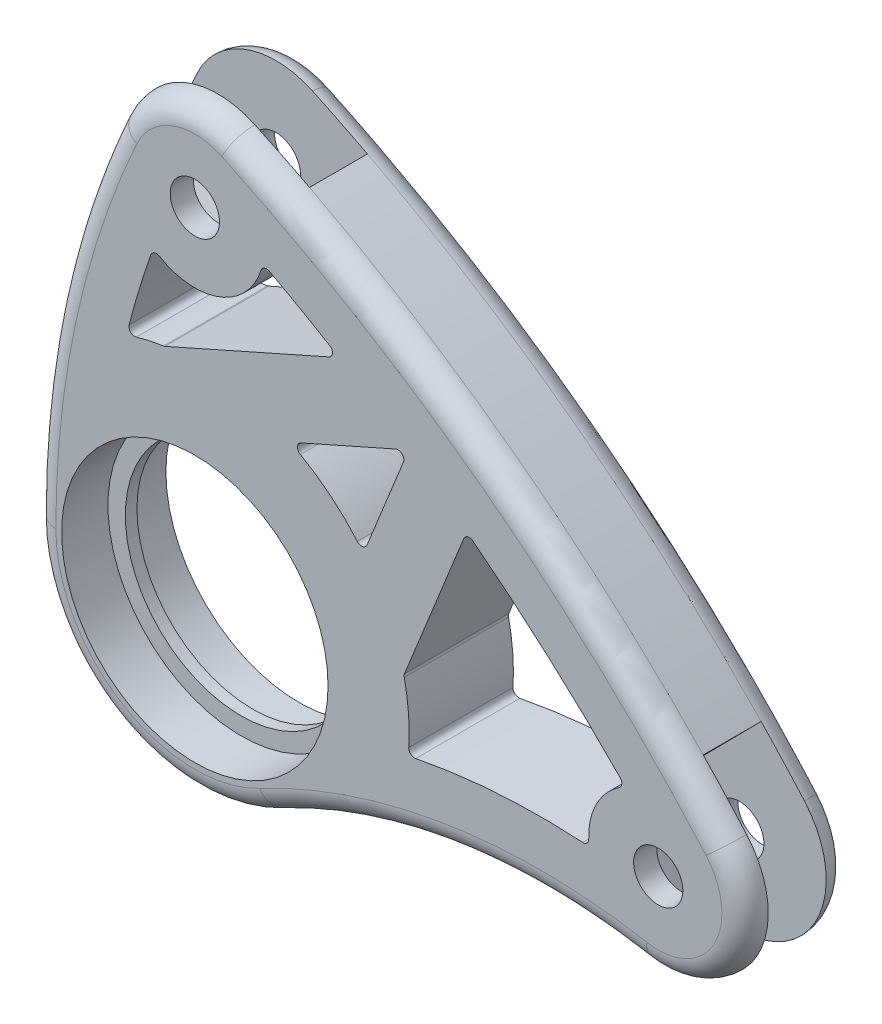
SolidWorks part; units mm, degrees
ref_plane "Front Plane" through (0, 0, 0) normal (0, 0, 1) x (1, 0, 0)
ref_plane "Top Plane" through (0, 0, 0) normal (0, 1, 0) x (1, 0, 0)
ref_plane "Right Plane" through (0, 0, 0) normal (1, 0, 0) x (0, 0, -1)
sketch "Sketch1" plane through (0, 0, 0) normal (0, 0, 1) x (1, 0, 0)
  line L0 (0, 0) -> (0, 55.2821) construction
  line L2 (40, 0) -> (0, 0) construction
  line L4 (0, 30) -> (0, 0) construction
  circle A0 centre (0, 0) radius 11.5
  circle A1 centre (0, 0) radius 14
  circle A2 centre (0, 30) radius 7.5
  circle A3 centre (40, 0) radius 7.5
  arc A4 (6.5345, -12.3815) -> (38.6789, -7.3827) centre (29.8719, -56.601) cw
  arc A5 (-6.8276, 33.1039) -> (-14, 0.0009) centre (66, -0.0042) ccw
  arc A6 (3.1808, 36.7921) -> (45.6298, 4.9554) centre (-51.9531, -80.9375) cw
  dimension "D1" = 23
  dimension "D2" = 28
  dimension "D5" = 90
  dimension "D6" = 80
  dimension "D7" = 50
  dimension "D8" = 130
  dimension "D9" = 15
  dimension "D3" = 40
  dimension "D4" = 30
extrude "Boss-Extrude1" add sketch "Sketch1" along normal blind 9 contours A6 A2 A5 A1 A4 A3 | A2 | A3 | A0 | A1 A0 region at (0, 0, 0) region at (11.6501, -7.0245, 0) region at (15.8028, 12.5336, 0) region at (0, 30, 0) region at (40, 0, 0)
sketch "Sketch2" plane through (0, 0, 9) normal (0, 0, 1) x (1, 0, 0)
  circle A4 centre (0, 0) radius 10
  dimension "D1" = 20
extrude "Cut-Extrude2" cut sketch "Sketch2" against normal through all contours A4 region at (0, 0, 9)
sketch "Sketch3" plane through (0, 0, 9) normal (0, 0, 1) x (1, 0, 0)
  circle A0 centre (0, 0) radius 11.5
  dimension "D1" = 23
extrude "Cut-Extrude3" cut sketch "Sketch3" against normal blind 4
sketch "Sketch4" plane through (0, 0, 0) normal (0, 0, -1) x (-1, 0, 0)
  circle A0 centre (0, 0) radius 11.5
  dimension "D1" = 23
extrude "Cut-Extrude4" cut sketch "Sketch4" against normal blind 4
sketch "Sketch6" plane through (0, 0, 9) normal (0, 0, 1) x (1, 0, 0)
  circle A0 centre (0, 30) radius 2.125
  circle A1 centre (40, 0) radius 2.125
  dimension "D1" = 4.25
extrude "Cut-Extrude5" cut sketch "Sketch6" against normal through all contours A1 | A0 region at (40, 0, 9)
sketch "Sketch7" plane through (0, 0, 9) normal (0, 0, 1) x (1, 0, 0)
  line L1 (18.4682, 21.1255) -> (14.5474, 11.4291)
  line L2 (-6.0691, 16.79) -> (12.4582, 25.0209)
  line L3 (23.4691, 17.4876) -> (15.3839, -2.5076)
  line L4 (18.4682, 21.1255) -> (10.8736, 2.3437) construction
  line L5 (-11.4565, 14.3966) -> (29.5935, 32.6335) construction
  line L6 (29.5935, 32.6335) -> (16.436, 0.0944) construction
  line L7 (-9.0205, 8.9133) -> (18.4682, 21.1255) construction
  line L8 (8.221, 16.573) -> (18.4682, 21.1255)
  circle A0 centre (0, 30) radius 6
  circle A1 centre (40, 0) radius 6
  arc A30 (-1.3655, 30.6208) -> (-8, 0.0005) centre (66, -0.0042) ccw
  arc A31 (-1.3655, 30.6208) -> (-8, 0.0005) centre (66, -0.0042) ccw
  arc A33 (41.126, 0.9911) -> (0.6362, 31.3584) centre (-51.9531, -80.9375) ccw
  arc A34 (41.126, 0.9911) -> (0.6362, 31.3584) centre (-51.9531, -80.9375) ccw
  arc A36 (39.7358, -1.4765) -> (3.734, -7.0751) centre (29.8719, -56.601) ccw
  arc A37 (39.7358, -1.4765) -> (3.734, -7.0751) centre (29.8719, -56.601) ccw
  circle A39 centre (0, 0) radius 18.5
  circle A41 centre (0, 0) radius 11.5 construction
  dimension "D1" = 12
  dimension "D5" = 7
  dimension "D6" = 6
  dimension "D2" = 6
  dimension "D3" = 6
  dimension "D4" = 6
extrude "Cut-Extrude6" cut sketch "Sketch7" against normal through all contours L2 A34 A0 A31 | A39 L1 L8 | A37 A1 A34 L3 region at (13.891, 16.5205, 9) region at (26.465, 6.1187, 9) region at (2.3721, 23.0253, 9)
fillet "Fillet1" radius 0.5 13 edges at (34.0479, -0.7569, 4.5) (37.1618, 5.2863, 4.5) (18.4136, -1.7858, 4.5) (5.8695, 28.7555, 4.5) (-3.5807, 25.1856, 4.5) (-5.8909, 17.537, 4.5) (14.5474, 11.4291, 4.5) (8.221, 16.573, 4.5) (23.4691, 17.4876, 4.5) (18.4682, 21.1255, 4.5) (12.4582, 25.0209, 4.5) (-2.6491, 18.3094, 4.5) (18.0456, 4.075, 4.5)
ref_plane "Plane1" through (0, 0, 4.5) normal (0, 0, 1) x (1, 0, 0)
sketch "Sketch8" plane through (0, 0, 4.5) normal (0, 0, 1) x (1, 0, 0)
  line L0 (36.4413, 3.5122) -> (41.8867, 9.0296)
  line L1 (35.4207, -2.0074) -> (37.705, -7.2184)
  line L2 (4.451, 27.7222) -> (7.901, 34.4639)
  line L3 (-2.0547, 25.4417) -> (-8.7629, 28.4654)
  circle A0 centre (40, 0) radius 5
  arc A1 (-14, 0.0009) -> (6.5345, -12.3815) centre (0, 0) ccw construction
  arc A2 (-6.8276, 33.1039) -> (-14, 0.0009) centre (66, -0.0042) ccw construction
  arc A3 (3.1808, 36.7921) -> (-6.8276, 33.1039) centre (0, 30) ccw construction
  arc A4 (38.6789, -7.3827) -> (6.5345, -12.3815) centre (29.8719, -56.601) ccw construction
  arc A5 (38.6789, -7.3827) -> (45.6298, 4.9554) centre (40, 0) ccw construction
  arc A6 (45.6298, 4.9554) -> (3.1808, 36.7921) centre (-51.9531, -80.9375) ccw construction
  arc A7 (-14, 0.0009) -> (6.5345, -12.3815) centre (0, 0) ccw
  arc A8 (-6.8276, 33.1039) -> (-14, 0.0009) centre (66, -0.0042) ccw
  arc A9 (3.1808, 36.7921) -> (-6.8276, 33.1039) centre (0, 30) ccw
  arc A10 (38.6789, -7.3827) -> (6.5345, -12.3815) centre (29.8719, -56.601) ccw
  arc A11 (38.6789, -7.3827) -> (45.6298, 4.9554) centre (40, 0) ccw
  arc A12 (45.6298, 4.9554) -> (3.1808, 36.7921) centre (-51.9531, -80.9375) ccw
  circle A13 centre (0, 30) radius 5
  dimension "D1" = 10
  dimension "D2" = 10
extrude "Cut-Extrude7" cut sketch "Sketch8" against normal blind 2.5 and the other way blind 2.5 contours A13 L2 A12 A9 A8 L3 | A13 | A0 | A11 A12 L0 A0 L1 A10 region at (39.3098, 6.1271, 4.5) region at (40, 0, 4.5) region at (5.9929, 31.1868, 4.5) region at (0, 30, 4.5)
fillet "Fillet2" radius 2 12 edges at (-2.5934, 37.0374, 0) (-12.1858, 16.9363, 0) (-7.2294, -11.989, 0) (22.1888, -7.1948, 0) (46.5344, -3.6812, 0) (-2.5934, 37.0374, 9) (-12.1858, 16.9363, 9) (-7.2294, -11.989, 9) (22.1888, -7.1948, 9) (46.5344, -3.6812, 9) (26.0469, 23.0625, 0) (26.0469, 23.0625, 9)
